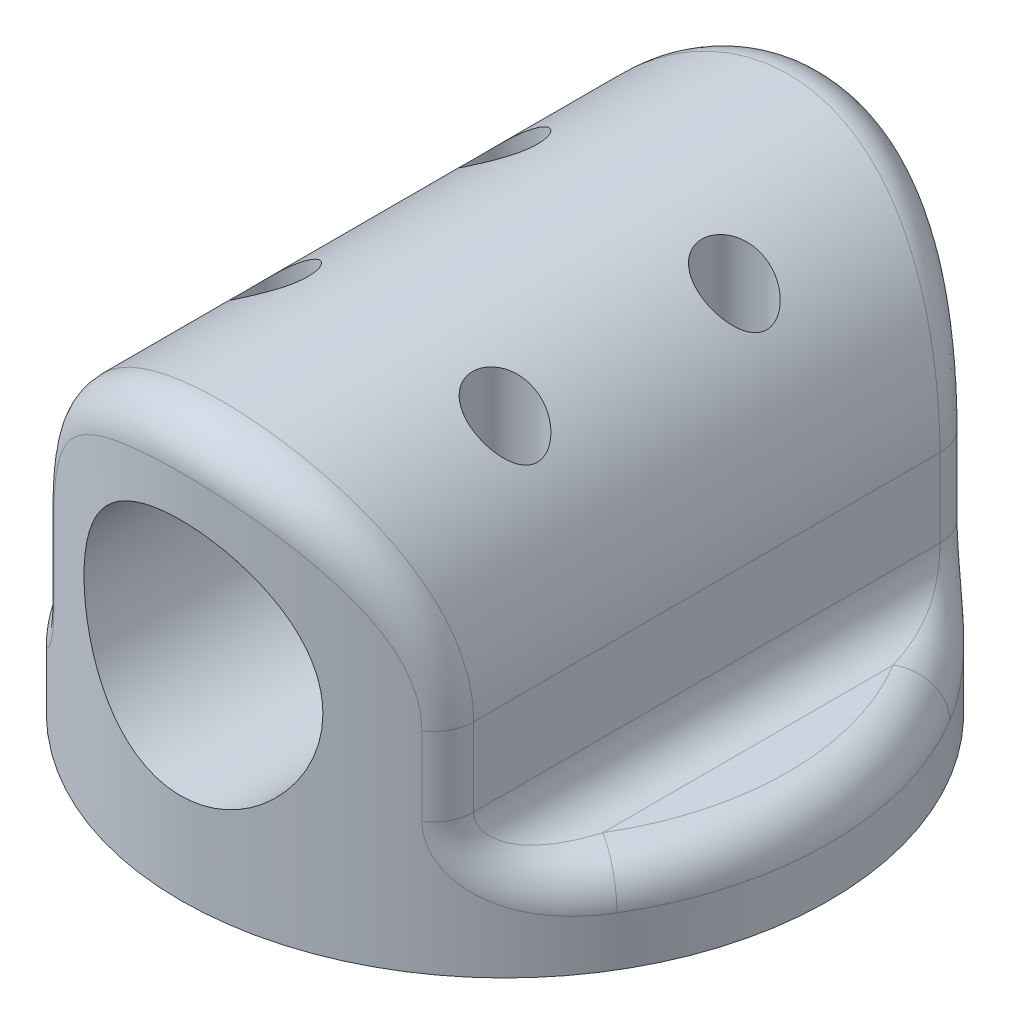
SolidWorks part; units mm, degrees
ref_plane "Front Plane" through (0, 0, 0) normal (0, 0, 1) x (1, 0, 0)
ref_plane "Top Plane" through (0, 0, 0) normal (0, 1, 0) x (1, 0, 0)
ref_plane "Right Plane" through (0, 0, 0) normal (1, 0, 0) x (0, 0, -1)
sketch "Sketch1" plane through (0, 0, 0) normal (0, 1, 0) x (1, 0, 0)
  circle A0 centre (0, 0) radius 30
  dimension "D1" = 60
extrude "Motor plate" add sketch "Sketch1" along normal mid plane 38.1
sketch "Sketch2" plane through (0, 0, 0) normal (0, 0, 1) x (1, 0, 0)
  line L0 (30, 19.05) -> (-30, 19.05) construction
  line L1 (-18.669, 0.381) -> (18.669, 0.381) construction
  line L2 (-30, -10.668) -> (-30, 19.05)
  line L3 (-30, 19.05) -> (-30, -19.05) construction
  line L5 (30, 19.05) -> (30, -10.668)
  line L6 (30, -19.05) -> (30, 19.05) construction
  line L7 (-30, -10.668) -> (-18.669, -10.668)
  line L8 (-18.669, -10.668) -> (-18.669, 0.381)
  line L9 (30, -10.668) -> (18.669, -10.668)
  line L10 (18.669, -10.668) -> (18.669, 0.381)
  line L11 (0, 0.381) -> (0, -10.668) construction
  line L12 (-30, 19.05) -> (-30, 27.2464)
  line L13 (-30, 27.2464) -> (30, 27.2464)
  line L14 (30, 27.2464) -> (30, 19.05)
  circle A0 centre (0, 0.381) radius 11.049
  arc A1 (18.669, 0.381) -> (-18.669, 0.381) centre (0, 0.381) ccw
  dimension "D1" = 22.098
  dimension "D2" = 18.669
extrude "Basic shape and spar hole" cut sketch "Sketch2" against normal through all both and the other way through all
sketch "Sketch3" plane through (0, -19.05, 0) normal (0, -1, 0) x (1, 0, 0)
  line L0 (-10.6066, 10.6066) -> (0, 0) construction
  line L1 (0, 0) -> (-15, 0) construction
  circle A0 centre (0, 0) radius 15 construction
  circle A1 centre (-10.6066, 10.6066) radius 1.5
  circle A2 centre (10.6066, 10.6066) radius 1.5
  circle A3 centre (10.6066, -10.6066) radius 1.5
  circle A4 centre (-10.6066, -10.6066) radius 1.5
  point P15 (0, 0)
  dimension "D1" = 30
  dimension "D2" = 3
  dimension "D3" = 45
  dimension "D4" = 4
extrude "Screwhole pt1" cut sketch "Sketch3" against normal through all both and the other way through all
sketch "Sketch4" plane through (0, 0, 0) normal (0, 1, 0) x (1, 0, 0)
  circle A0 centre (-10.6066, 10.6066) radius 3
  circle A1 centre (0, 0) radius 15 construction
  circle A2 centre (10.6066, 10.6066) radius 3
  circle A3 centre (10.6066, -10.6066) radius 3
  circle A4 centre (-10.6066, -10.6066) radius 3
  point P15 (0, 0)
  dimension "D1" = 6
  dimension "D2" = 4
extrude "Screwhole pt2" cut sketch "Sketch4" against normal blind 15 and the other way through all
fillet "Fillet1" radius 3.81 10 edges at (-30, -10.668, 0) (-18.669, -5.1435, -23.4834) (-18.669, -5.1435, 23.4834) (0, 19.05, -30) (-0.5664, 19.0414, 29.9947) (18.669, -5.1435, -23.4834) (18.669, -5.1435, 23.4834) (30, -10.668, 0) (18.669, -10.668, 0) (-18.669, -10.668, 0)
